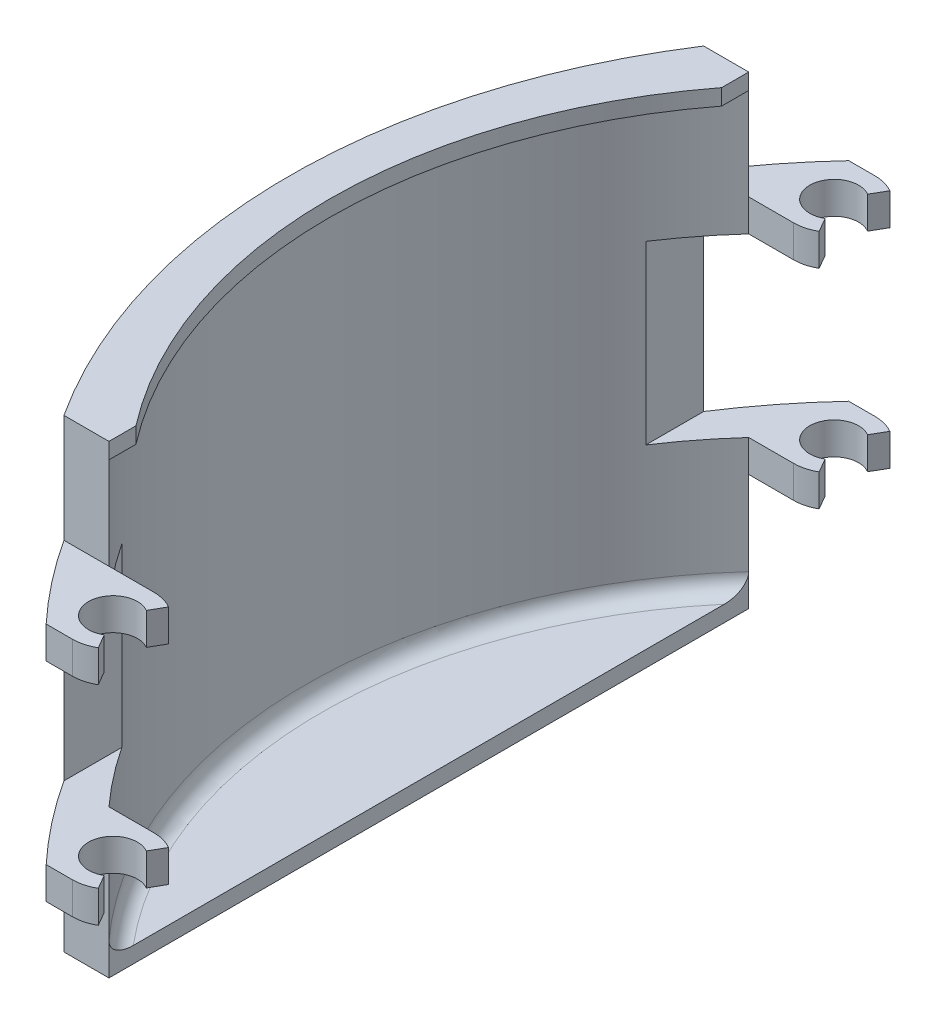
SolidWorks part; units mm, degrees
ref_plane "Front Plane" through (0, 0, 0) normal (0, 0, 1) x (1, 0, 0)
ref_plane "Top Plane" through (0, 0, 0) normal (0, 1, 0) x (1, 0, 0)
ref_plane "Right Plane" through (0, 0, 0) normal (1, 0, 0) x (0, 0, -1)
sketch "Sketch2" plane through (0, 0, 0) normal (0, 1, 0) x (1, 0, 0)
  line L2 (3.4168, 51.52) -> (43.1499, 51.52) construction
  line L3 (0.0958, 91.44) -> (5.6838, 91.44)
  line L8 (2.4212, 101.6) -> (5.6838, 101.6)
  line L11 (2.4212, 1.44) -> (5.6838, 1.44)
  line L12 (0.0958, 11.6) -> (5.6838, 11.6)
  line L13 (-17.3407, 51.52) -> (-15.3407, 51.52) construction
  arc A2 (5.6838, 91.44) -> (5.6838, 101.6) centre (5.6838, 96.52) ccw
  circle A3 centre (5.6838, 96.52) radius 3.048
  circle A6 centre (5.6838, 6.52) radius 3.048
  arc A7 (5.6838, 11.6) -> (5.6838, 1.44) centre (5.6838, 6.52) cw
  arc A10 (2.4212, 1.44) -> (2.4212, 101.6) centre (55.9958, 51.52) cw
  arc A11 (0.0958, 11.6) -> (0.0958, 91.44) centre (43.9958, 51.52) cw
  dimension "D2" = 2
  dimension "D7" = 2.032
  dimension "D8" = 6.096
  dimension "D1" = 45
extrude "Boss-Extrude1" add sketch "Sketch2" along normal blind 56
sketch "Sketch6" plane through (0, 56, 0) normal (0, 1, 0) x (1, 0, 0)
  line L0 (-15.3407, 51.52) -> (43.9958, 51.52) construction
  line L1 (5.6838, 6.52) -> (11.4571, 16.5935)
  line L2 (11.4571, 16.5935) -> (11.4571, -3.4065)
  line L3 (11.4571, -3.4065) -> (5.6838, 6.52)
  arc A0 (0.0958, 91.44) -> (0.0958, 11.6) centre (43.9958, 51.52) ccw construction
  dimension "D1" = 120
  dimension "D2" = 20
ref_plane "Plane1" through (0, 0, -51.52) normal (0, 0, 1) x (1, 0, 0)
extrude "Cut-Extrude2" cut sketch "Sketch6" against normal through all both and the other way through all contours L1 L2 L3
mirror "Mirror1" about plane through (0, 0, -51.52) normal (0, 0, 1) of "Cut-Extrude2"
ref_plane "Plane2" through (5.6838, 56, -1.44) normal (0, -1, 0) x (-1, 0, 0)
sketch "Sketch12" plane through (0, 0, -1.44) normal (0, 0, 1) x (1, 0, 0)
  line L0 (2.4212, 56) -> (2.4212, 0) construction
  line L1 (2.4212, 40.5) -> (8.2378, 40.5)
  line L2 (2.4212, 40.5) -> (2.4212, 18.5)
  line L3 (2.4212, 18.5) -> (8.2378, 18.5)
  line L4 (8.2378, 40.5) -> (8.2378, 18.5)
  line L5 (8.2378, 56) -> (8.2378, 0) construction
  line L6 (-49.3162, 56) -> (60.6838, 56) construction
  line L7 (2.4212, 56) -> (8.2378, 56)
  line L8 (2.4212, 56) -> (2.4212, 44.5)
  line L9 (2.4212, 44.5) -> (8.2378, 44.5)
  line L10 (8.2378, 56) -> (8.2378, 44.5)
  line L12 (2.4212, 0) -> (8.2378, 0)
  line L13 (2.4212, 0) -> (2.4212, 14.5)
  line L14 (2.4212, 14.5) -> (8.2378, 14.5)
  line L15 (8.2378, 0) -> (8.2378, 14.5)
  point P19 (5.3295, 44.5)
  dimension "D1" = 30
  dimension "D2" = 11.5
  dimension "D3" = 22
  dimension "D4" = 4
extrude "Cut-Extrude3" cut sketch "Sketch12" against normal through all both and the other way through all
sketch "Sketch13" plane through (2.4212, 0, 0) normal (1, 0, 0) x (0, 0, -1)
  line L0 (101.6, 56) -> (101.6, 44.5) construction
  line L1 (11.6, 44.5) -> (1.44, 44.5)
  line L2 (11.6, 44.5) -> (11.6, 56)
  line L3 (11.6, 56) -> (1.44, 56)
  line L4 (1.44, 44.5) -> (1.44, 56)
  line L5 (1.44, 14.5) -> (11.6, 14.5)
  line L6 (1.44, 14.5) -> (1.44, 0)
  line L7 (1.44, 0) -> (11.6, 0)
  line L8 (11.6, 14.5) -> (11.6, 0)
  line L9 (91.44, 56) -> (101.6, 56)
  line L10 (91.44, 56) -> (91.44, 44.5)
  line L11 (91.44, 44.5) -> (101.6, 44.5)
  line L12 (101.6, 56) -> (101.6, 44.5)
  line L14 (101.6, 0) -> (91.44, 0)
  line L15 (101.6, 0) -> (101.6, 14.5)
  line L16 (101.6, 14.5) -> (91.44, 14.5)
  line L17 (91.44, 0) -> (91.44, 14.5)
extrude "Cut-Extrude4" cut sketch "Sketch13" against normal blind 10
fillet "Fillet1" radius 10 2 edges at (2.4212, 29.5, -91.44) (2.4212, 29.5, -11.6)
sketch "Sketch15" plane through (0, 0, 0) normal (0, -1, 0) x (-1, 0, 0)
  line L0 (-0.0958, 11.6) -> (-0.0958, 91.44)
  arc A0 (-0.0958, 91.44) -> (-0.0958, 11.6) centre (-43.9958, 51.52) cw
extrude "Boss-Extrude2" add sketch "Sketch15" against normal blind 2
fillet "Fillet2" radius 2 1 edges at (-15.3407, 2, -51.52)
sketch "Sketch17" plane through (0, 56, 0) normal (0, 1, 0) x (1, 0, 0)
  line L0 (0.0958, 11.6) -> (5.6838, 11.6) construction
  line L1 (5.6838, 91.44) -> (0.0958, 91.44) construction
  line L2 (2.8898, 91.44) -> (-5.5236, 91.44)
  line L3 (2.8898, 11.6) -> (-5.5236, 11.6)
  line L4 (-17.3407, 51.52) -> (-12.3407, 51.52) construction
  arc A0 (2.8898, 11.6) -> (2.8898, 91.44) centre (47.5909, 51.52) cw
  arc A2 (-5.5236, 11.6) -> (-5.5236, 91.44) centre (55.9958, 51.52) cw
  dimension "D1" = 5
extrude "Boss-Extrude3" add sketch "Sketch17" along normal blind 2
sketch "Sketch18" plane through (0, 58, 0) normal (0, 1, 0) x (1, 0, 0)
  line L1 (0.0958, 11.6) -> (2.9741, 11.6)
  line L2 (0.0958, 11.6) -> (0.0958, 15.1418)
  line L3 (0.0958, 15.1418) -> (2.9741, 15.1418)
  line L4 (2.9741, 11.6) -> (2.9741, 15.1418)
  line L5 (0.0958, 91.44) -> (3.2623, 91.44)
  line L6 (0.0958, 91.44) -> (0.0958, 87.8553)
  line L7 (0.0958, 87.8553) -> (3.2623, 87.8553)
  line L8 (3.2623, 91.44) -> (3.2623, 87.8553)
extrude "Cut-Extrude5" cut sketch "Sketch18" against normal blind 2
sketch "Sketch19" plane through (0, 0, -11.6) normal (0, 0, 1) x (1, 0, 0)
  line L0 (2.4212, 18.5) -> (-17.3407, 18.5) construction
  line L1 (2.4212, 40.5) -> (-5.5207, 40.5)
  line L2 (2.4212, 40.5) -> (2.4212, 18.5)
  line L3 (2.4212, 18.5) -> (-5.5207, 18.5)
  line L4 (-5.5207, 40.5) -> (-5.5207, 18.5)
  line L7 (-17.3407, 44.5) -> (-17.3407, 18.5) construction
  dimension "D1" = 11.82
extrude "Cut-Extrude7" cut sketch "Sketch19" against normal through all both and the other way through all
